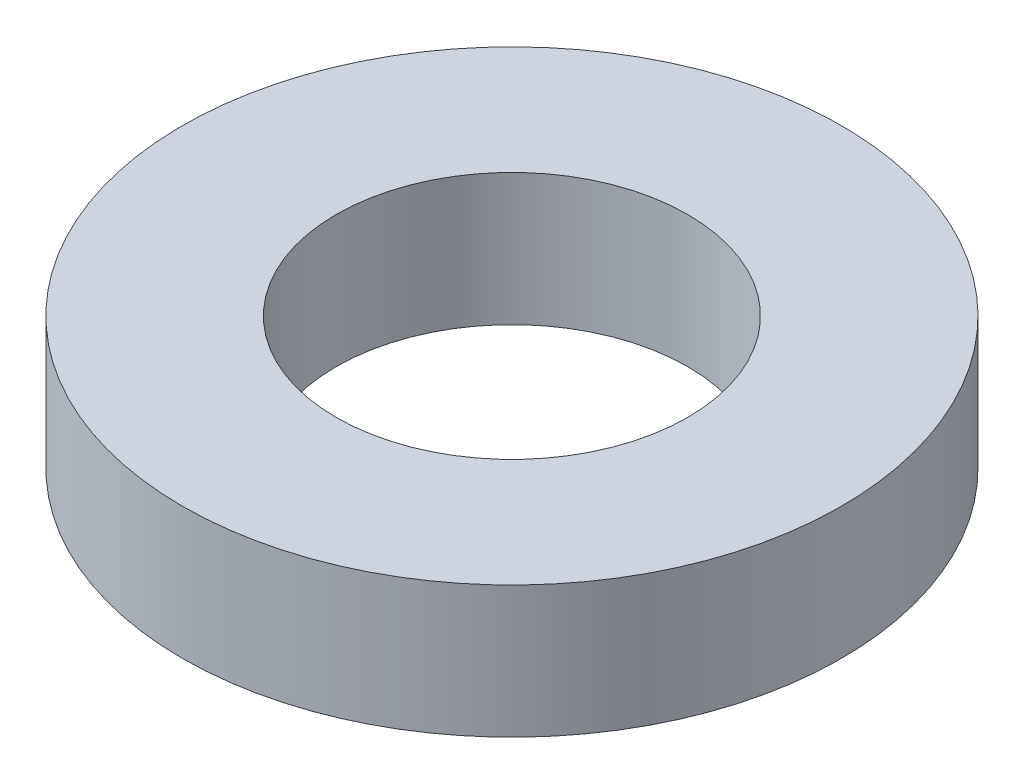
SolidWorks part; units mm, degrees
ref_plane "Front Plane" through (0, 0, 0) normal (0, 0, 1) x (1, 0, 0)
ref_plane "Top Plane" through (0, 0, 0) normal (0, 1, 0) x (1, 0, 0)
ref_plane "Right Plane" through (0, 0, 0) normal (1, 0, 0) x (0, 0, -1)
sketch "Sketch1" plane through (0, 0, 0) normal (0, 1, 0) x (1, 0, 0)
  circle A0 centre (0, 0) radius 75
  dimension "FLANGE_OD" = 150
extrude "Boss-Extrude1" add sketch "Sketch1" along normal blind 30
sketch "Sketch2" plane through (0, 0, 0) normal (0, 1, 0) x (1, 0, 0)
  circle A0 centre (0, 0) radius 40
  dimension "BORE_D" = 80
extrude "Cut-Extrude1" cut sketch "Sketch2" along normal through all
sketch "Sketch3" plane through (0, 30, 0) normal (0, 1, 0) x (1, 0, 0)
  circle A0 centre (0, 0) radius 24.569 construction
  circle A1 centre (-24.569, 0) radius 3.6534
  dimension "BOLT_D" = 7.3069
  dimension "BOLT_PCD" = 49.138
extrude "Cut-Extrude2" cut sketch "Sketch3" against normal blind 28.4008 rebuild error yes
pattern_circular "CirPattern1" count 5 over 360 rebuild error yes
